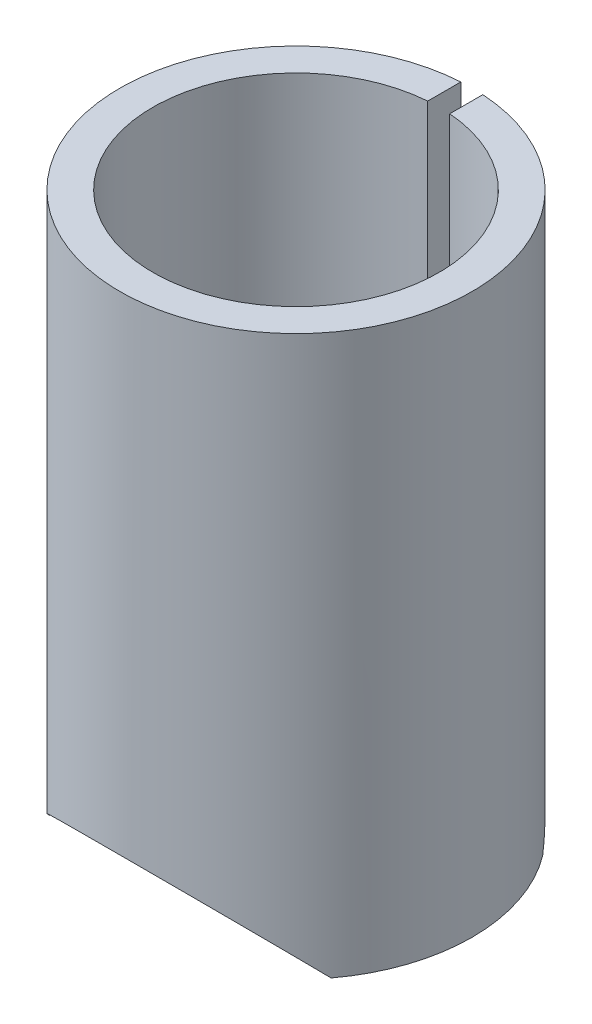
SolidWorks part; units mm, degrees
ref_plane "Front Plane" through (0, 0, 0) normal (0, 0, 1) x (1, 0, 0)
ref_plane "Top Plane" through (0, 0, 0) normal (0, 1, 0) x (1, 0, 0)
ref_plane "Right Plane" through (0, 0, 0) normal (1, 0, 0) x (0, 0, -1)
sketch "Sketch1" plane through (0, 0, 0) normal (0, 1, 0) x (1, 0, 0)
  line L0 (-1, 14.4651) -> (1, 14.4651) construction
  line L2 (-1, 15.9687) -> (-1, 12.9615)
  line L4 (1, 15.9687) -> (1, 12.9615)
  arc A0 (-1, 12.9615) -> (1, 12.9615) centre (0, 0) ccw
  arc A1 (-1, 15.9687) -> (1, 15.9687) centre (0, 0) ccw
  dimension "D1" = 26
  dimension "D2" = 3
  dimension "D3" = 2
extrude "Boss-Extrude1" add sketch "Sketch1" along normal blind 50.8
sketch "Sketch2" plane through (0, 0, 0) normal (0, 0, 1) x (1, 0, 0)
  line L1 (0, 0) -> (0, -9.3986) construction
  circle A1 centre (0, -9.3986) radius 15.875
  circle A2 centre (0, 0) radius 12.7 construction
  point P1 (0, -9.3986)
  point P6 (0, 11.2207)
  point P8 (0, 0)
  dimension "D1" = 31.75
  dimension "D2" = 25.4
extrude "Cut-Extrude1" cut sketch "Sketch2" against normal blind 50.8 and the other way blind 50.8
